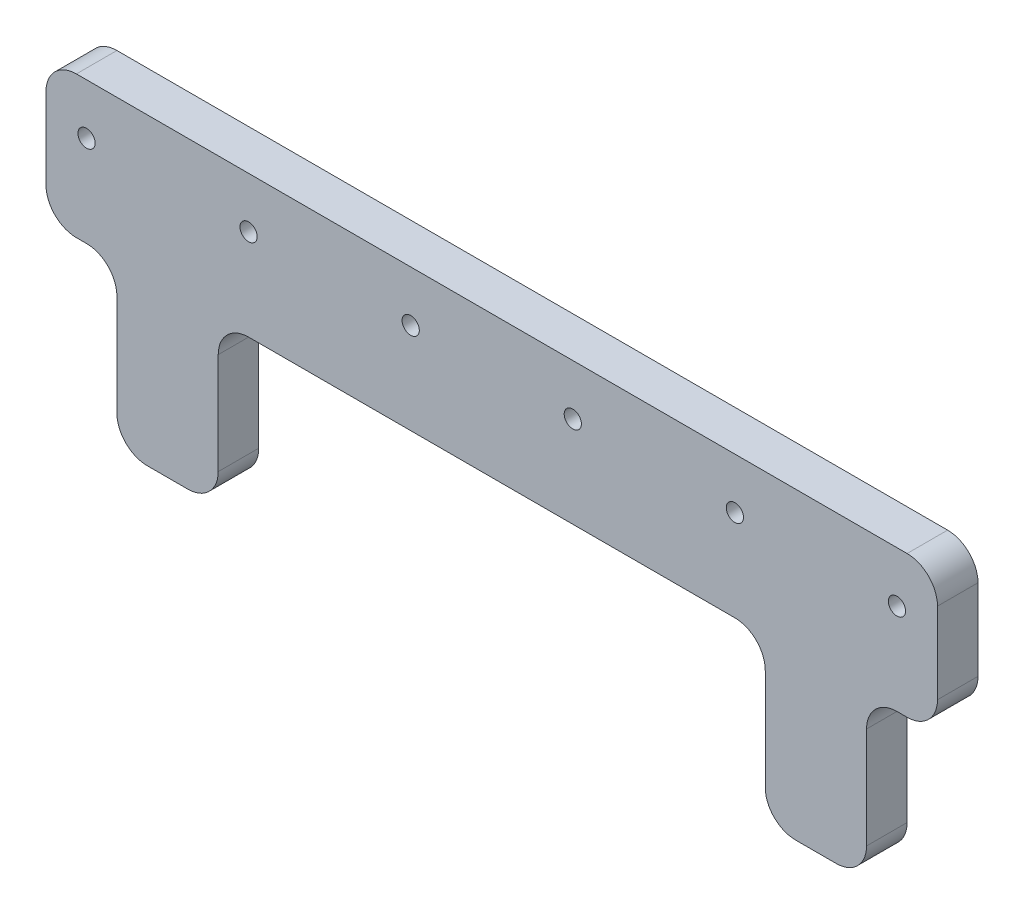
SolidWorks part; units mm, degrees
ref_plane "Top" through (0, 0, 0) normal (0, 0, 1) x (1, 0, 0)
ref_plane "Front" through (0, 0, 0) normal (0, 1, 0) x (1, 0, 0)
ref_plane "Right" through (0, 0, 0) normal (1, 0, 0) x (0, 0, -1)
sketch "Base Sketch" plane through (0, 0, 0) normal (0, 0, 1) x (1, 0, 0)
  line L0 (-44, 7) -> (44, -7) construction
  line L1 (-44, 7) -> (44, 7)
  line L2 (-44, 7) -> (-44, -7)
  line L3 (-44, -7) -> (44, -7)
  line L4 (44, 7) -> (44, -7)
  point P4 (0, 0)
  dimension "D1" = 88
  dimension "D2" = 14
extrude "Base Extrude" add sketch "Base Sketch" against normal blind 4
sketch "Pin Hole Sketch" plane through (0, 0, 0) normal (0, 0, 1) x (1, 0, 0)
  line L0 (44, -7) -> (44, 7) construction
  line L1 (44, 7) -> (-44, 7) construction
  circle A0 centre (40, 2) radius 0.85
  dimension "D3" = 1.7
  dimension "D1" = 4
  dimension "D2" = 5
extrude "First Pin Hole Cut" cut sketch "Pin Hole Sketch" against normal through all
pattern_linear "Pin Hole Pattern" count 6 spacing 16 along (-1, 0, 0) of "First Pin Hole Cut"
sketch "Extension Sketch" plane through (0, 0, 0) normal (0, 0, 1) x (1, 0, 0)
  line L0 (-40, 2) -> (-24, 2) construction
  line L1 (-32, 2) -> (-32, -23) construction
  line L2 (-37, -23) -> (-27, -23)
  line L3 (-27, -23) -> (-27, 2)
  line L4 (-27, 2) -> (-37, 2)
  line L5 (-37, 2) -> (-37, -23)
  line L6 (44, 7) -> (-44, 7) construction
  dimension "D1" = 10
  dimension "D2" = 30
extrude "Tab Extrude" add sketch "Extension Sketch" against normal through all separate body
mirror "Tab Mirror" about plane through (0, 0, 0) normal (1, 0, 0) of "Tab Extrude"
combine bodies "Combine Bodies" operation type add bodies to combine 106 105
fillet "Corner Fillets" radius 3 12 edges at (44, 7, -2) (44, -7, -2) (-44, -7, -2) (-44, 7, -2) (-37, -7, -2) (27, -7, -2) (37, -7, -2) (-27, -7, -2) (27, -23, -2) (37, -23, -2) (-37, -23, -2) (-27, -23, -2)
